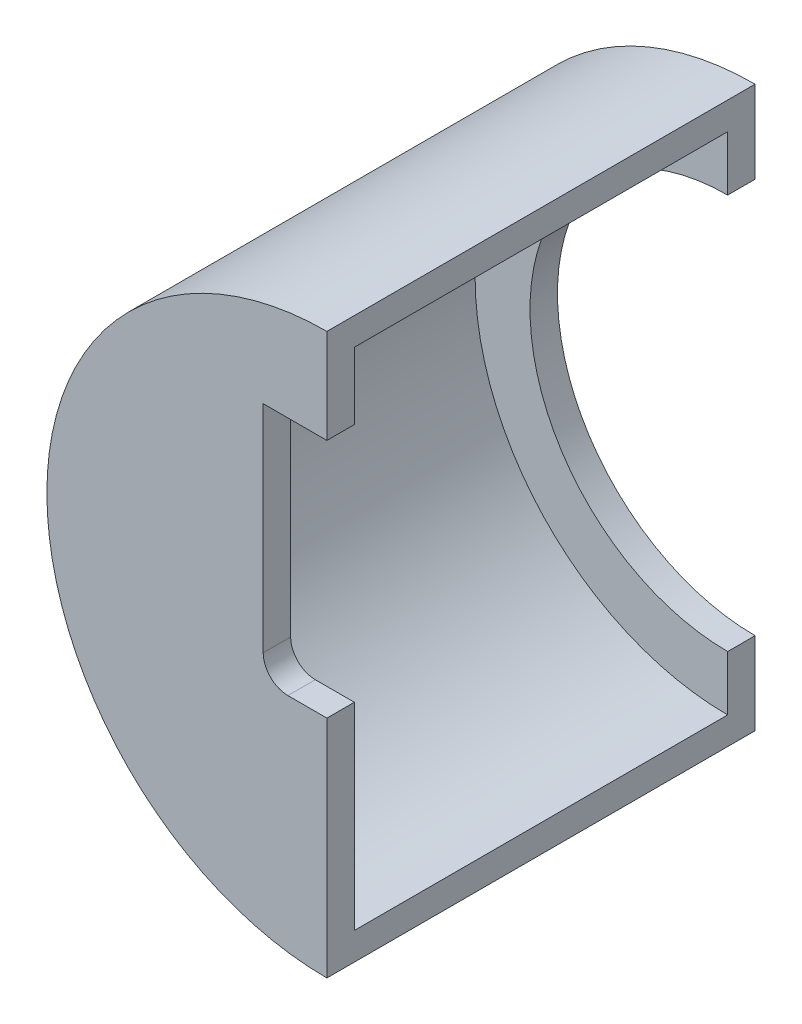
SolidWorks part; units mm, degrees
ref_plane "Plan de face" through (0, 0, 0) normal (0, 0, 1) x (1, 0, 0)
ref_plane "Plan de dessus" through (0, 0, 0) normal (0, 1, 0) x (1, 0, 0)
ref_plane "Plan de droite" through (0, 0, 0) normal (1, 0, 0) x (0, 0, -1)
sketch "Esquisse1" plane through (0, 0, 0) normal (0, 0, 1) x (1, 0, 0)
  line L0 (0, 54.1543) -> (0, -54.1543) construction
  line L1 (-103.4367, 0) -> (52.1834, 0) construction
  line L2 (0, 51) -> (0, 46)
  line L3 (0, -46) -> (0, -51)
  arc A0 (0, 46) -> (0, -46) centre (0, 0) ccw
  arc A1 (0, 51) -> (0, -51) centre (0, 0) ccw
  dimension "D1" = 46
  dimension "D2" = 5
extrude "Boss.-Extru.1" add sketch "Esquisse1" along normal mid plane 68
sketch "Esquisse2" plane through (0, 0, 34) normal (0, 0, 1) x (1, 0, 0)
  line L0 (0, 51) -> (0, -51)
  arc A0 (0, 51) -> (0, -51) centre (0, 0) ccw
  arc A1 (0, 51) -> (0, -51) centre (0, 0) ccw construction
extrude "Boss.-Extru.2" add sketch "Esquisse2" along normal blind 5
sketch "Esquisse3" plane through (0, 0, -34) normal (0, 0, -1) x (-1, 0, 0)
  line L0 (0, 51) -> (0, 36)
  line L1 (0, -51) -> (0, -36)
  arc A0 (0, -51) -> (0, 51) centre (0, 0) ccw
  arc A1 (0, -51) -> (0, 51) centre (0, 0) ccw construction
  arc A2 (0, -36) -> (0, 36) centre (0, 0) ccw
  arc A3 (0, -46) -> (0, 46) centre (0, 0) ccw construction
  dimension "D1" = 10
extrude "Boss.-Extru.3" add sketch "Esquisse3" along normal blind 5
sketch "Esquisse4" plane through (0, 0, 39) normal (0, 0, 1) x (1, 0, 0)
  line L0 (-35.4912, 0) -> (41.3624, 0) construction
  line L1 (-11.6, -2) -> (11.6, -2)
  line L2 (-11.6, -2) -> (-11.6, -33.8)
  line L3 (-11.6, -33.8) -> (11.6, -33.8)
  line L4 (11.6, -2) -> (11.6, -33.8)
  line L5 (-11.6, -2) -> (-11.6, 5.5)
  line L6 (11.6, -2) -> (11.6, 5.5)
  line L7 (-7.1, 10) -> (7.1, 10)
  line L8 (-7.1, -10) -> (7.1, -10)
  line L9 (11.6, 2) -> (11.6, -5.5)
  line L10 (-11.6, 2) -> (-11.6, -5.5)
  line L11 (11.6, 2) -> (11.6, 33.8)
  line L12 (-11.6, 33.8) -> (11.6, 33.8)
  line L13 (-11.6, 2) -> (-11.6, 33.8)
  line L14 (-11.6, 2) -> (11.6, 2)
  arc A0 (-11.6, 5.5) -> (-7.1, 10) centre (-7.1, 5.5) cw
  arc A1 (7.1, 10) -> (11.6, 5.5) centre (7.1, 5.5) cw
  circle A2 centre (0, 0) radius 2.15
  circle A3 centre (0, 0) radius 2.15
  arc A4 (7.1, -10) -> (11.6, -5.5) centre (7.1, -5.5) ccw
  arc A5 (-11.6, -5.5) -> (-7.1, -10) centre (-7.1, -5.5) ccw
  line M18 (0, -51) -> (0, 51)
  dimension "D3" = 4.3
  dimension "D6" = 4.5
  dimension "D7" = 4.5
  dimension "D1" = 2
  dimension "D2" = 11.6
  dimension "D4" = 43.8
  dimension "D5" = 23.2
  dimension "D8" = 12
extrude "Enlèv. mat.-Extru.1" cut sketch "Esquisse4" against normal blind 10 contours L13 A0 L7 L12 M18 | A2 L7 A0 L5 L14 M18 | L10 L0 A2 L14 | L0 L5 L1 A3 | L2 A5 L8 A2 L1 M18 | L0 A3 L1 M18 | A2 L0 L14 M18 | A2 region at (-6.6808, 1.0205, 39) region at (-6.6808, -1.0205, 39) region at (-0.9263, 0.8868, 39) region at (-0.9263, -0.8868, 39) region at (-5.5692, -5.8563, 39) region at (-5.5692, 5.8563, 39) region at (-5.8743, 21.7, 39)
